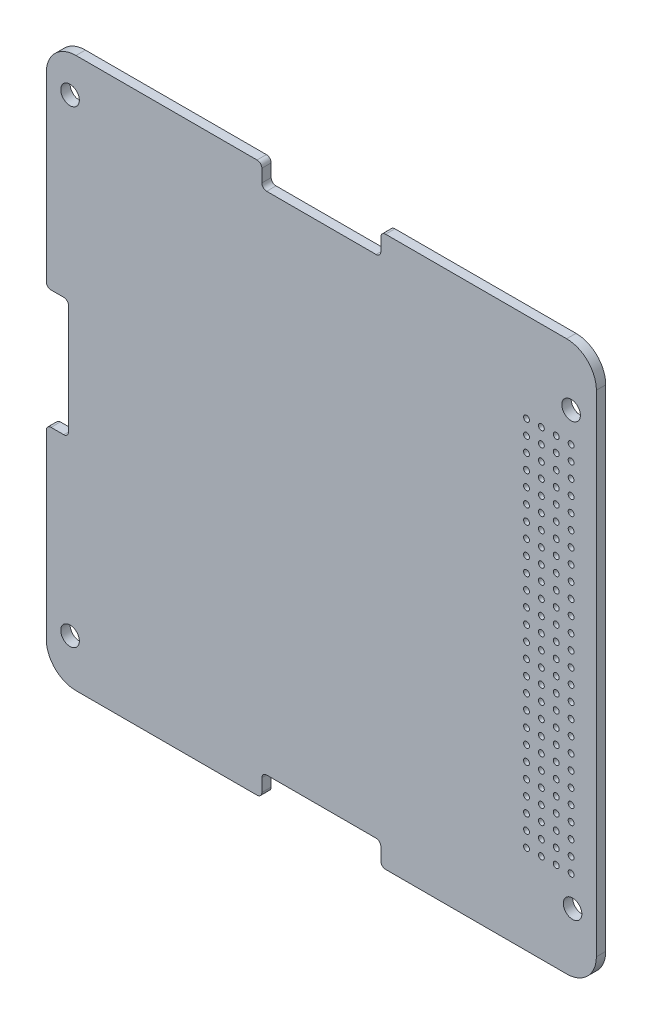
SolidWorks part; units mm, degrees
ref_plane "Front Plane" through (0, 0, 0) normal (0, 0, 1) x (1, 0, 0)
ref_plane "Top Plane" through (0, 0, 0) normal (0, 1, 0) x (1, 0, 0)
ref_plane "Right Plane" through (0, 0, 0) normal (1, 0, 0) x (0, 0, -1)
sketch "Sketch1" plane through (0, 0, 0) normal (0, 0, 1) x (1, 0, 0)
  line L0 (5.08, 0) -> (36.0124, 0)
  line L1 (36.83, 0.8176) -> (36.83, 2.9924)
  line L2 (37.6476, 3.81) -> (56.3324, 3.81)
  line L3 (57.15, 2.9924) -> (57.15, 0.8176)
  line L4 (57.9676, 0) -> (88.9, 0)
  line L5 (93.98, 5.08) -> (93.98, 88.9)
  line L6 (88.9, 93.98) -> (57.9676, 93.98)
  line L7 (57.15, 93.1624) -> (57.15, 90.9876)
  line L8 (56.3324, 90.17) -> (37.6476, 90.17)
  line L9 (36.83, 90.9876) -> (36.83, 93.1624)
  line L10 (36.0124, 93.98) -> (5.08, 93.98)
  line L11 (0, 88.9) -> (0, 57.9676)
  line L12 (0.8176, 57.15) -> (2.9924, 57.15)
  line L13 (3.81, 56.3324) -> (3.81, 37.6476)
  line L14 (2.9924, 36.83) -> (0.8176, 36.83)
  line L15 (0, 36.0124) -> (0, 5.08)
  arc A0 (5.08, 0) -> (0, 5.08) centre (5.08, 5.08) cw
  arc A1 (88.9, 0) -> (93.98, 5.08) centre (88.9, 5.08) ccw
  arc A2 (93.98, 88.9) -> (88.9, 93.98) centre (88.9, 88.9) ccw
  arc A3 (5.08, 93.98) -> (0, 88.9) centre (5.08, 88.9) ccw
  arc A4 (57.15, 0.8176) -> (57.9676, 0) centre (57.9676, 0.8176) ccw
  arc A5 (56.3324, 3.81) -> (57.15, 2.9924) centre (56.3324, 2.9924) cw
  arc A6 (36.83, 2.9924) -> (37.6476, 3.81) centre (37.6476, 2.9924) cw
  arc A7 (36.0124, 0) -> (36.83, 0.8176) centre (36.0124, 0.8176) ccw
  arc A8 (0.8176, 36.83) -> (0, 36.0124) centre (0.8176, 36.0124) ccw
  arc A9 (3.81, 37.6476) -> (2.9924, 36.83) centre (2.9924, 37.6476) cw
  arc A10 (2.9924, 57.15) -> (3.81, 56.3324) centre (2.9924, 56.3324) cw
  arc A11 (0, 57.9676) -> (0.8176, 57.15) centre (0.8176, 57.9676) ccw
  arc A12 (36.83, 93.1624) -> (36.0124, 93.98) centre (36.0124, 93.1624) ccw
  arc A13 (37.6476, 90.17) -> (36.83, 90.9876) centre (37.6476, 90.9876) cw
  arc A14 (57.15, 90.9876) -> (56.3324, 90.17) centre (56.3324, 90.9876) cw
  arc A15 (57.9676, 93.98) -> (57.15, 93.1624) centre (57.9676, 93.1624) ccw
  circle A16 centre (82.042, 78.74) radius 0.5
  circle A17 centre (84.582, 78.74) radius 0.5
  circle A18 centre (87.122, 78.74) radius 0.5
  circle A19 centre (89.662, 78.74) radius 0.5
  circle A20 centre (84.582, 76.2) radius 0.5
  circle A21 centre (87.122, 76.2) radius 0.5
  circle A22 centre (89.662, 76.2) radius 0.5
  circle A23 centre (84.582, 73.66) radius 0.5
  circle A24 centre (87.122, 73.66) radius 0.5
  circle A25 centre (89.662, 73.66) radius 0.5
  circle A26 centre (84.582, 71.12) radius 0.5
  circle A27 centre (87.122, 71.12) radius 0.5
  circle A28 centre (89.662, 71.12) radius 0.5
  circle A29 centre (84.582, 68.58) radius 0.5
  circle A30 centre (87.122, 68.58) radius 0.5
  circle A31 centre (89.662, 68.58) radius 0.5
  circle A32 centre (84.582, 66.04) radius 0.5
  circle A33 centre (87.122, 66.04) radius 0.5
  circle A34 centre (89.662, 66.04) radius 0.5
  circle A35 centre (84.582, 63.5) radius 0.5
  circle A36 centre (87.122, 63.5) radius 0.5
  circle A37 centre (89.662, 63.5) radius 0.5
  circle A38 centre (84.582, 60.96) radius 0.5
  circle A39 centre (87.122, 60.96) radius 0.5
  circle A40 centre (89.662, 60.96) radius 0.5
  circle A41 centre (84.582, 58.42) radius 0.5
  circle A42 centre (87.122, 58.42) radius 0.5
  circle A43 centre (89.662, 58.42) radius 0.5
  circle A44 centre (84.582, 55.88) radius 0.5
  circle A45 centre (87.122, 55.88) radius 0.5
  circle A46 centre (89.662, 55.88) radius 0.5
  circle A47 centre (84.582, 53.34) radius 0.5
  circle A48 centre (87.122, 53.34) radius 0.5
  circle A49 centre (89.662, 53.34) radius 0.5
  circle A50 centre (84.582, 50.8) radius 0.5
  circle A51 centre (87.122, 50.8) radius 0.5
  circle A52 centre (89.662, 50.8) radius 0.5
  circle A53 centre (84.582, 48.26) radius 0.5
  circle A54 centre (87.122, 48.26) radius 0.5
  circle A55 centre (89.662, 48.26) radius 0.5
  circle A56 centre (84.582, 45.72) radius 0.5
  circle A57 centre (87.122, 45.72) radius 0.5
  circle A58 centre (89.662, 45.72) radius 0.5
  circle A59 centre (84.582, 43.18) radius 0.5
  circle A60 centre (87.122, 43.18) radius 0.5
  circle A61 centre (89.662, 43.18) radius 0.5
  circle A62 centre (84.582, 40.64) radius 0.5
  circle A63 centre (87.122, 40.64) radius 0.5
  circle A64 centre (89.662, 40.64) radius 0.5
  circle A65 centre (84.582, 38.1) radius 0.5
  circle A66 centre (87.122, 38.1) radius 0.5
  circle A67 centre (89.662, 38.1) radius 0.5
  circle A68 centre (84.582, 35.56) radius 0.5
  circle A69 centre (87.122, 35.56) radius 0.5
  circle A70 centre (89.662, 35.56) radius 0.5
  circle A71 centre (84.582, 33.02) radius 0.5
  circle A72 centre (87.122, 33.02) radius 0.5
  circle A73 centre (89.662, 33.02) radius 0.5
  circle A74 centre (84.582, 30.48) radius 0.5
  circle A75 centre (87.122, 30.48) radius 0.5
  circle A76 centre (89.662, 30.48) radius 0.5
  circle A77 centre (84.582, 27.94) radius 0.5
  circle A78 centre (87.122, 27.94) radius 0.5
  circle A79 centre (89.662, 27.94) radius 0.5
  circle A80 centre (84.582, 25.4) radius 0.5
  circle A81 centre (87.122, 25.4) radius 0.5
  circle A82 centre (89.662, 25.4) radius 0.5
  circle A83 centre (84.582, 22.86) radius 0.5
  circle A84 centre (87.122, 22.86) radius 0.5
  circle A85 centre (89.662, 22.86) radius 0.5
  circle A86 centre (84.582, 20.32) radius 0.5
  circle A87 centre (87.122, 20.32) radius 0.5
  circle A88 centre (89.662, 20.32) radius 0.5
  circle A89 centre (84.582, 17.78) radius 0.5
  circle A90 centre (87.122, 17.78) radius 0.5
  circle A91 centre (89.662, 17.78) radius 0.5
  circle A92 centre (84.582, 15.24) radius 0.5
  circle A93 centre (87.122, 15.24) radius 0.5
  circle A94 centre (89.662, 15.24) radius 0.5
  circle A95 centre (82.042, 76.2) radius 0.5
  circle A96 centre (82.042, 73.66) radius 0.5
  circle A97 centre (82.042, 71.12) radius 0.5
  circle A98 centre (82.042, 68.58) radius 0.5
  circle A99 centre (82.042, 66.04) radius 0.5
  circle A100 centre (82.042, 63.5) radius 0.5
  circle A101 centre (82.042, 60.96) radius 0.5
  circle A102 centre (82.042, 58.42) radius 0.5
  circle A103 centre (82.042, 55.88) radius 0.5
  circle A104 centre (82.042, 53.34) radius 0.5
  circle A105 centre (82.042, 50.8) radius 0.5
  circle A106 centre (82.042, 48.26) radius 0.5
  circle A107 centre (82.042, 45.72) radius 0.5
  circle A108 centre (82.042, 43.18) radius 0.5
  circle A109 centre (82.042, 40.64) radius 0.5
  circle A110 centre (82.042, 38.1) radius 0.5
  circle A111 centre (82.042, 35.56) radius 0.5
  circle A112 centre (82.042, 33.02) radius 0.5
  circle A113 centre (82.042, 30.48) radius 0.5
  circle A114 centre (82.042, 27.94) radius 0.5
  circle A115 centre (82.042, 25.4) radius 0.5
  circle A116 centre (82.042, 22.86) radius 0.5
  circle A117 centre (82.042, 20.32) radius 0.5
  circle A118 centre (82.042, 17.78) radius 0.5
  circle A119 centre (82.042, 15.24) radius 0.5
  circle A120 centre (89.916, 10.16) radius 1.5875
  circle A121 centre (89.662, 83.82) radius 1.5875
  circle A123 centre (4.064, 7.62) radius 1.5875
  circle A124 centre (4.064, 87.63) radius 1.5875
  point P20 (0, 0)
  point P268 (0, 0)
  point P272 (0, 0)
  dimension "D7" = 5.08
  dimension "D8" = 0.8176
  dimension "D9" = 1
  dimension "D12" = 80.01
  dimension "D18" = 3.175
  dimension "D19" = 3.81
  dimension "D1" = 93.98
  dimension "D2" = 93.98
  dimension "D3" = 36.83
  dimension "D4" = 3.81
  dimension "D5" = 3.81
  dimension "D6" = 3.81
  dimension "D13" = 73.66
  dimension "D14" = 5.08
  dimension "D15" = 15.24
  dimension "D16" = 85.598
  dimension "D17" = 85.852
  dimension "D20" = 4.064
  dimension "D10" = 4
  dimension "D11" = 26
extrude "Boss-Extrude2" add sketch "Sketch1" along normal blind 1.6
hole_wizard "Mounting holes" positions "3DSketch4" profile "Sketch5" hole size "1/8" standard "ANSI Inch" end condition through all
sketch3d "3DSketch4"
  line L0 (4.064, 87.63, 1.6) -> (4.064, 87.63, 0) construction
  line L1 (89.662, 83.82, 1.6) -> (89.662, 83.82, 0) construction
  line L2 (89.916, 10.16, 1.6) -> (89.916, 10.16, 0) construction
  line L3 (4.064, 7.62, 1.6) -> (4.064, 7.62, 0) construction
  point P0 (4.064, 87.63, 1.6)
  point P4 (89.662, 83.82, 1.6)
  point P8 (89.916, 10.16, 1.6)
  point P12 (4.064, 7.62, 1.6)
sketch "Sketch5" plane through (4.064, 87.63, 1.6) normal (1, 0, 0) x (0, -1, 0)
  line L0 (0, 0) -> (0, 1.6)
  line L1 (0, 1.6) -> (1.5875, 1.6)
  line L2 (1.5875, 1.6) -> (1.5875, 0)
  line L5 (1.5875, 0) -> (0, 0)
  line L11 (0, -6.35) -> (0, 107.95) construction
  dimension "Thru Hole Dia." = 3.175
  dimension "Thru Hole Depth" = 1.6
